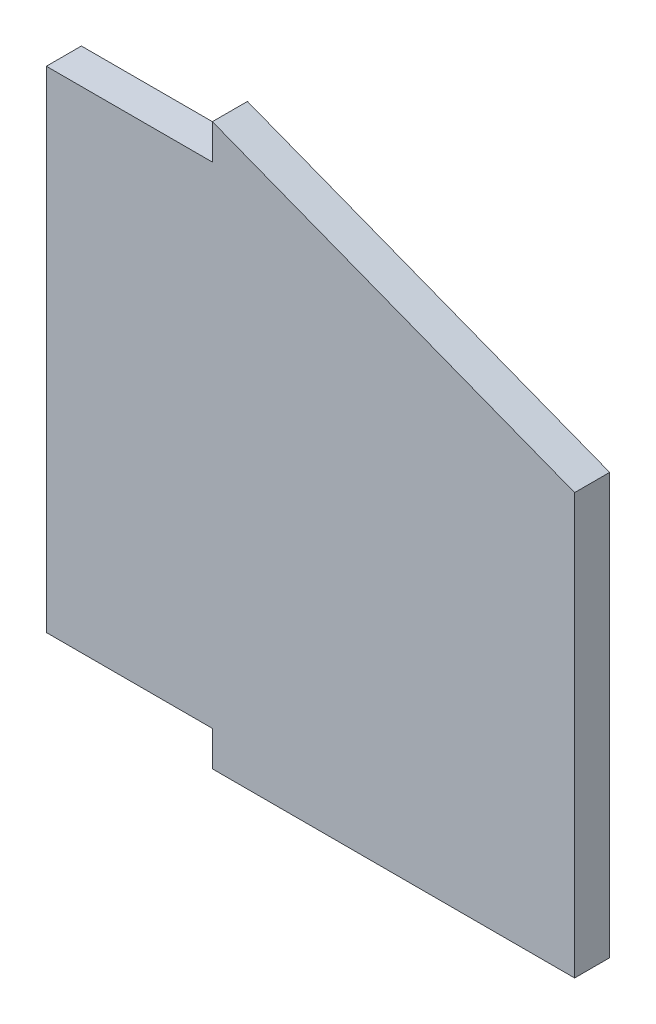
SolidWorks part; units mm, degrees
ref_plane "Front Plane" through (0, 0, 0) normal (0, 0, 1) x (1, 0, 0)
ref_plane "Top Plane" through (0, 0, 0) normal (0, 1, 0) x (1, 0, 0)
ref_plane "Right Plane" through (0, 0, 0) normal (1, 0, 0) x (0, 0, -1)
sketch "Sketch1" plane through (0, 0, 0) normal (0, 0, 1) x (1, 0, 0)
  line L0 (0, 0) -> (0, 70)
  line L1 (0, 70) -> (23.7, 70)
  line L5 (75.4, -5) -> (23.7, -5)
  line L6 (23.7, -5) -> (23.7, 0)
  line L7 (23.7, 0) -> (0, 0)
  line L8 (23.7, 70) -> (23.7, 75)
  line L9 (23.7, 75) -> (75.4, 55)
  line L10 (75.4, 55) -> (75.4, -5)
  line L11 (23.7, 75) -> (23.7, -5) construction
  point P3 (23.7, 35)
  point P10 (0, 35)
  dimension "D1" = 80
  dimension "D2" = 60
  dimension "D3" = 51.7
  dimension "D4" = 23.7
  dimension "D5" = 70
extrude "Boss-Extrude1" add sketch "Sketch1" along normal blind 5
